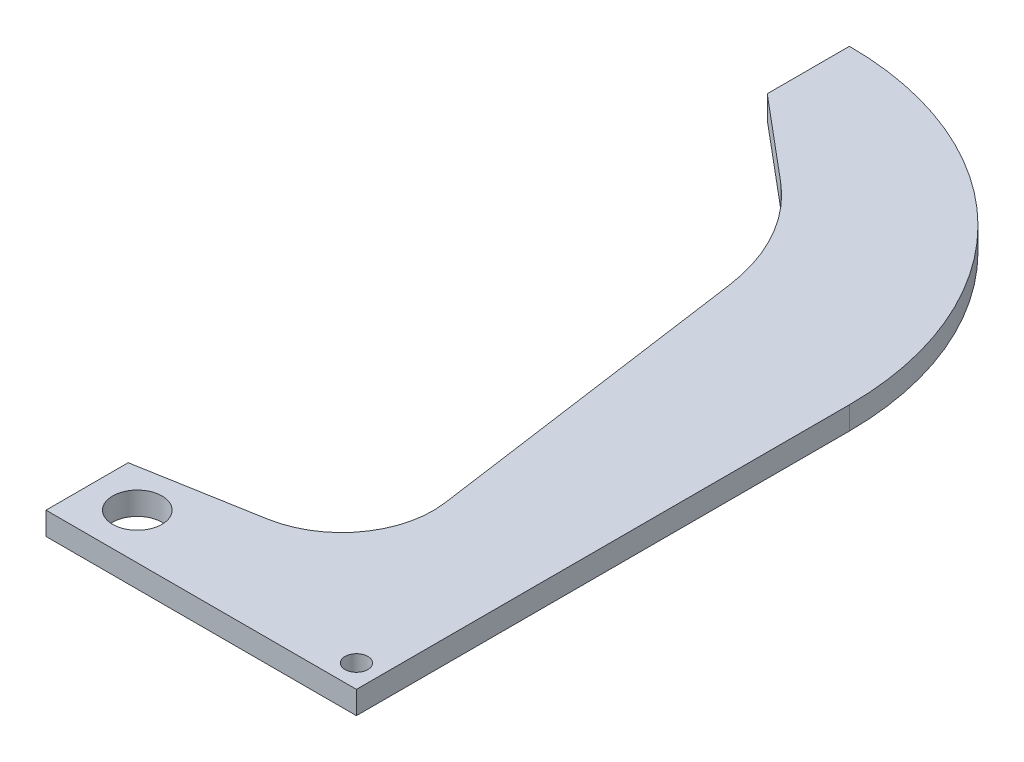
SolidWorks part; units mm, degrees
ref_plane "Front Plane" through (0, 0, 0) normal (0, 0, 1) x (1, 0, 0)
ref_plane "Top Plane" through (0, 0, 0) normal (0, 1, 0) x (1, 0, 0)
ref_plane "Right Plane" through (0, 0, 0) normal (1, 0, 0) x (0, 0, -1)
sketch "Sketch1" plane through (0, 0, 0) normal (0, 1, 0) x (1, 0, 0)
  line L1 (0, 0) -> (43.18, 0)
  line L2 (0, 0) -> (0, 111.76)
  line L4 (43.18, 0) -> (43.18, 68.58)
  circle A0 centre (6.35, 6.35) radius 3.429
  circle A1 centre (40.005, 3.175) radius 1.5875
  arc A2 (43.18, 68.58) -> (0, 111.76) centre (0, 68.58) ccw
  dimension "D3" = 6.858
  dimension "D6" = 3.175
  dimension "D1" = 43.18
  dimension "D4" = 6.35
  dimension "D5" = 6.35
  dimension "D7" = 3.175
  dimension "D8" = 3.175
  dimension "D2" = 111.76
extrude "Boss-Extrude1" add sketch "Sketch1" along normal blind 3.175
sketch "Sketch2" plane through (0, 3.175, 0) normal (0, 1, 0) x (1, 0, 0)
  line L1 (0, 111.76) -> (0, 0) construction
  line L2 (16.4996, 14.3393) -> (0, 11.43)
  line L3 (0, 11.43) -> (0, 100.33)
  line L4 (26.871, 28.6113) -> (20.4054, 74.6866)
  line L5 (11.5786, 90.6144) -> (0, 100.33)
  arc A0 (20.4054, 74.6866) -> (11.5786, 90.6144) centre (-4.7482, 71.1568) ccw
  arc A1 (26.871, 28.6113) -> (16.4996, 14.3393) centre (14.2943, 26.8464) cw
  point P11 (19.05, 84.3452)
  point P14 (28.575, 16.4685)
  dimension "D7" = 25.4
  dimension "D8" = 12.7
  dimension "D1" = 88.9
  dimension "D2" = 11.43
  dimension "D3" = 50
  dimension "D4" = 80
  dimension "D5" = 19.05
  dimension "D6" = 28.575
extrude "Cut-Extrude1" cut sketch "Sketch2" against normal through all
equation "\"tightTol\" = 0.005in"
equation "\"normTol\"= 0.01in"
equation "\"looseTol\"= 0.02in"
equation "\"D3@Sketch1\"=\"looseTol\"+0.25"
